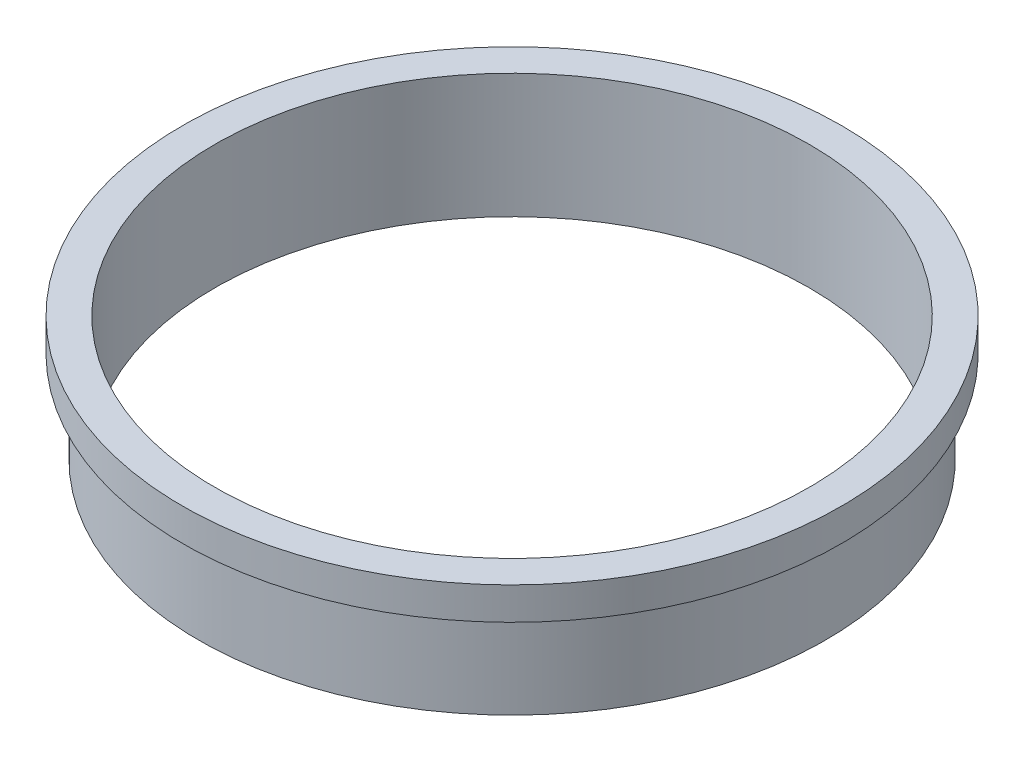
SolidWorks part; units mm, degrees
ref_plane "Front Plane" through (0, 0, 0) normal (0, 0, 1) x (1, 0, 0)
ref_plane "Top Plane" through (0, 0, 0) normal (0, 1, 0) x (1, 0, 0)
ref_plane "Right Plane" through (0, 0, 0) normal (1, 0, 0) x (0, 0, -1)
sketch "Sketch1" plane through (0, 0, 0) normal (0, 0, 1) x (1, 0, 0)
  line L0 (0, 0) -> (0, 20)
  line L2 (27.5, 0) -> (29, 0)
  line L3 (27.5, 0) -> (27.5, 11.5)
  line L4 (27.5, 11.5) -> (29, 11.5)
  line L5 (29, 0) -> (29, 11.5)
  line L6 (29, 11.5) -> (30.5, 11.5)
  line L7 (29, 11.5) -> (29, 8.5)
  line L8 (29, 8.5) -> (30.5, 8.5)
  line L9 (30.5, 11.5) -> (30.5, 8.5)
  dimension "D1" = 11.5
  dimension "D2" = 27.5
  dimension "D3" = 1.5
  dimension "D4" = 1.5
  dimension "D5" = 3
revolve "Revolve1" add sketch "Sketch1" angle 360 about L0 region at (28.25, 5.75, 0) region at (29.75, 10, 0)
